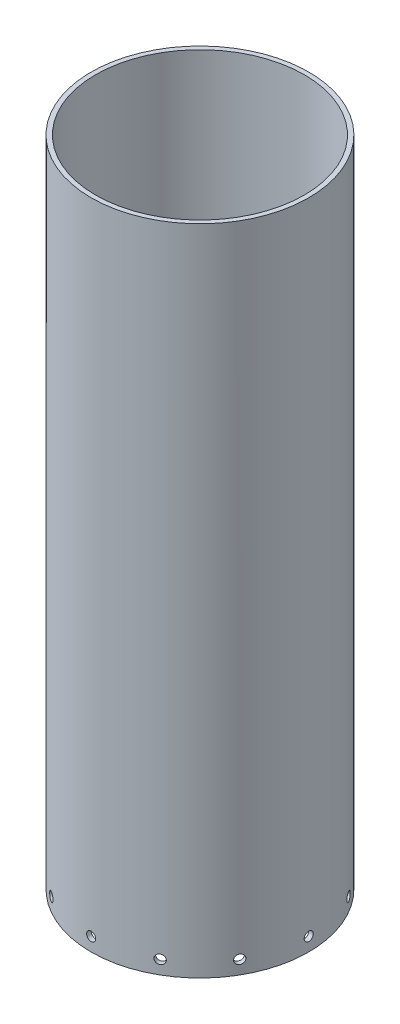
SolidWorks part; units mm, degrees
material "Polycarbonate"
ref_plane "Front Plane" through (0, 0, 0) normal (0, 0, 1) x (1, 0, 0)
ref_plane "Top Plane" through (0, 0, 0) normal (0, 1, 0) x (1, 0, 0)
ref_plane "Right Plane" through (0, 0, 0) normal (1, 0, 0) x (0, 0, -1)
sketch "Sketch2" plane through (0, 0, 0) normal (0, 1, 0) x (1, 0, 0)
  circle A0 centre (0, 0) radius 73.025
  circle A1 centre (0, 0) radius 76.2
  dimension "D1" = 146.05
  dimension "D2" = 152.4
extrude "Boss-Extrude1" add sketch "Sketch2" along normal blind 457.2
sketch "Sketch3" plane through (0, 0, 0) normal (0, 0, 1) x (1, 0, 0)
  line L0 (0, 0) -> (0, 235.745) construction
  line L1 (-76.2, 0) -> (76.2, 0) construction
  circle A0 centre (0, 9.525) radius 3.175
  dimension "D1" = 9.525
extrude "Cut-Extrude1" cut sketch "Sketch3" against normal through all
ref_axis "Axis1" through (0, 0, 0) along (0, 1, 0)
pattern_circular "CirPattern1" count 12 over 360 about axis through (0, 0, 0) along (0, 1, 0) of "Cut-Extrude1"
